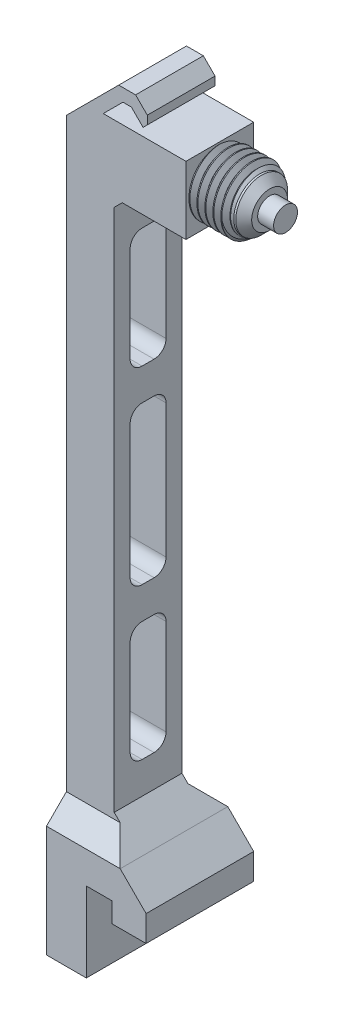
SolidWorks part; units mm, degrees
ref_plane "Front Plane" through (0, 0, 0) normal (0, 0, 1) x (1, 0, 0)
ref_plane "Top Plane" through (0, 0, 0) normal (0, 1, 0) x (1, 0, 0)
ref_plane "Right Plane" through (0, 0, 0) normal (1, 0, 0) x (0, 0, -1)
sketch "Sketch1" plane through (0, 0, 0) normal (0, 0, 1) x (1, 0, 0)
  line L0 (-13, 0) -> (13, 0) construction
  line L1 (-3, 12) -> (-3, -12) construction
  line L2 (-13, 12) -> (-13, -12) construction
  line L3 (13, 8) -> (13, -8) construction
  point P8 (6, -8)
  dimension "Thread Dia" = 16
  dimension "Hex" = 24
  dimension "Head Ht" = 10
  dimension "Length" = 16
  dimension "D1" = 7
ref_plane "Plane2" through (13, 0, 0) normal (1, 0, 0) x (0, 0, -1)
sketch "Sketch2" plane through (13, 0, 0) normal (1, 0, 0) x (0, 0, -1)
  circle A0 centre (0, 0) radius 8
extrude "Boss-Extrude1" add sketch "Sketch2" against normal up to vertex (16 mm away) up to point (-3, -12, 0)
sketch "Sketch4" plane through (13, 0, 0) normal (1, 0, 0) x (0, 0, -1)
  circle A1 centre (0, 0) radius 8
  circle A2 centre (0, 0) radius 8
  dimension "D1" = 0
curve "Helix/Spiral1" pitch 2 height 18 turns 9 parameters "Pitch"=2
chamfer "Chamfer1" distance 1.5 angle 45 1 edges at (13, 0, -8)
sketch "Sketch5" plane through (0, 0, 0) normal (0, 0, 1) x (1, 0, 0)
  line L0 (13, 8) -> (13.75, 6.701)
  line L1 (13.75, 6.701) -> (14, 6.701)
  line L2 (14, 6.701) -> (14.75, 8)
  line L3 (13, 8) -> (14.75, 8)
  line L4 (13.875, 6.701) -> (13.875, 8) construction
  line L5 (13.375, 7.3505) -> (14.375, 7.3505) construction
  line L6 (13, -8) -> (13, 8) construction
  dimension "D1" = 60
  dimension "D2" = 0.25
  dimension "D3" = 1
sweep "Cut-Sweep1" cut profiles "Sketch5" path "Helix/Spiral1" align with end faces yes
sketch "Sketch3" plane through (-3, 0, 0) normal (-1, 0, 0) x (0, 0, 1)
  line L0 (0, 12) -> (0, -12) construction
  line L1 (-12, -6.9282) -> (0, -13.8564)
  line L2 (0, -13.8564) -> (12, -6.9282)
  line L3 (12, -6.9282) -> (12, 6.9282)
  line L4 (12, 6.9282) -> (0, 13.8564)
  line L5 (0, 13.8564) -> (-12, 6.9282)
  line L6 (-12, 6.9282) -> (-12, -6.9282)
  circle A0 centre (0, 0) radius 12 construction
extrude "Boss-Extrude2" add sketch "Sketch3" along normal up to vertex (10 mm away) up to point (-13, -12, 0)
sketch "Sketch6" plane through (-13, 0, 0) normal (-1, 0, 0) x (0, 0, 1)
  circle A0 centre (0, 0) radius 12 construction
  circle A1 centre (0, 0) radius 12
extrude "Cut-Extrude1" cut sketch "Sketch6" against normal through all draft 60 flip side to cut
sketch "Sketch7" plane through (-13, 0, 0) normal (-1, 0, 0) x (0, 0, 1)
  line L0 (0, 0) -> (0, 12) construction
  line L2 (0, 12) -> (0, -12) construction
  line L3 (-10.3923, 6) -> (10.3923, 6) construction
  circle A1 centre (0, 0) radius 12 construction
  text T0 "8.8\r\n" font "Arial" height in points 16
  point P8 (0, 6)
extrude "Cut-Extrude2" cut sketch "Sketch7" against normal blind 0.25
sketch "Sketch9" plane through (0, 0, 0) normal (0, 0, 1) x (1, 0, 0)
  line L0 (-3, 8) -> (-3, 0)
  line L1 (-3, 0) -> (-5, 0)
  line L2 (-5, 0) -> (-13, 8)
  line L3 (-13, 8) -> (-3, 8)
  line L4 (-13, 0) -> (13, 0) construction
  line L5 (-3, 12) -> (-3, -12) construction
  line L6 (13, 8) -> (13, -8) construction
  dimension "D1" = 45
  dimension "MinThreadLg" = 26
revolve "Revolve1" [suppressed] add sketch "Sketch9" angle 360 about L1
sketch "Sketch10" plane through (13, 0, 0) normal (1, 0, 0) x (0, 0, -1)
  circle A0 centre (0, 0) radius 6.5
extrude "Boss-Extrude3" add sketch "Sketch10" along normal blind 2.5
chamfer "Chamfer2" distance 2 angle 45 1 edges at (15.5, 0, -6.5)
sketch "Sketch11" plane through (15.5, 0, 0) normal (1, 0, 0) x (0, 0, -1)
  circle A0 centre (0, 0) radius 3
  dimension "D1" = 6
extrude "Boss-Extrude4" add sketch "Sketch11" along normal blind 4
sketch "Sketch13" plane through (-3, 0, 0) normal (1, 0, 0) x (0, 0, -1)
  line L1 (23.7718, -25.4479) -> (-27.8908, -25.4479)
  line L2 (23.7718, -25.4479) -> (23.7718, 26.4267)
  line L3 (23.7718, 26.4267) -> (-27.8908, 26.4267)
  line L4 (-27.8908, -25.4479) -> (-27.8908, 26.4267)
extrude "Cut-Extrude3" cut sketch "Sketch13" against normal blind 16 and the other way blind 6
sketch "Sketch14" plane through (3, 0, 0) normal (-1, 0, 0) x (0, 0, 1)
  line L1 (-8.5, -8.5) -> (8.5, -8.5)
  line L2 (-8.5, -8.5) -> (-8.5, 8.5)
  line L3 (-8.5, 8.5) -> (8.5, 8.5)
  line L4 (8.5, -8.5) -> (8.5, 8.5)
  line L5 (-8.5, -8.5) -> (8.5, 8.5) construction
  line L6 (-8.5, 8.5) -> (8.5, -8.5) construction
  point P0 (0, 0)
  dimension "D1" = 17
  dimension "D2" = 17
extrude "Boss-Extrude5" add sketch "Sketch14" along normal blind 30
sketch "Sketch15" plane through (0, -8.5, 0) normal (0, -1, 0) x (1, 0, 0)
  line L0 (-27, 8.5) -> (3, 8.5) construction
  line L1 (-27, -8.5) -> (-15, -8.5)
  line L2 (-27, -8.5) -> (-27, 8.5)
  line L3 (-27, 8.5) -> (-15, 8.5)
  line L4 (-15, -8.5) -> (-15, 8.5)
  dimension "D1" = 12
extrude "Boss-Extrude6" add sketch "Sketch15" along normal blind 140
chamfer "Chamfer3" distance 5 angle 45 1 edges at (-27, 8.5, 0)
sketch "Sketch17" plane through (0, 0, 8.5) normal (0, 0, 1) x (1, 0, 0)
  line L0 (-15, -148.5) -> (-15, -8.5) construction
  line L1 (-27, -148.5) -> (-7, -148.5)
  line L2 (-27, -148.5) -> (-27, -186.5)
  line L3 (-27, -186.5) -> (-17, -186.5)
  line L4 (-17, -156.5) -> (-17, -186.5)
  line L5 (-10.5, -161.5) -> (-2, -161.5)
  line L7 (-7, -148.5) -> (-2, -148.5)
  line L8 (-2, -161.5) -> (-2, -148.5)
  line L11 (-17, -156.5) -> (-10.5, -156.5)
  line L12 (-10.5, -161.5) -> (-10.5, -156.5)
  line M10 (-27, -148.5) -> (-15, -148.5)
  dimension "D1" = 6.5
  dimension "D2" = 5
  dimension "D3" = 13
  dimension "D4" = 10
  dimension "D5" = 25
  dimension "D6" = 13
extrude "Boss-Extrude7" add sketch "Sketch17" against normal blind 22 and the other way blind 5 contours L12 L5 L8 L7 L2 L3 L4 L11 M10
sketch "Sketch18" plane through (-27, 0, 0) normal (-1, 0, 0) x (0, 0, 1)
  line L1 (-13.5, -156.5) -> (13.5, -156.5) construction
  circle A0 centre (0, -164.5) radius 1.75
  dimension "D1" = 3.5
  dimension "D2" = 8
extrude "Cut-Extrude5" cut sketch "Sketch18" against normal blind 17
chamfer "Chamfer5" distance 2 angle 45 1 edges at (-15, -8.5, 0)
sketch "Sketch20" plane through (0, 0, 8.5) normal (0, 0, 1) x (1, 0, 0)
  line L0 (-22, 8.5) -> (-11.7574, 18.7426)
  line L1 (-11.7574, 14.5) -> (-7.7574, 10.5)
  line L2 (-7.7574, 10.5) -> (-5.636, 12.6213)
  line L3 (-5.636, 12.6213) -> (-11.7574, 18.7426)
  line L6 (-11.7574, 14.5) -> (-17.7574, 8.5)
  line L7 (-22, 8.5) -> (3, 8.5) construction
  line L8 (-17.7574, 8.5) -> (-22, 8.5)
  dimension "D1" = 3
  dimension "D2" = 3
  dimension "D3" = 2
  dimension "D4" = 6
extrude "Boss-Extrude8" add sketch "Sketch20" against normal blind 17
chamfer "Chamfer7" distance 1.5 angle 45 1 edges at (-11.7574, 14.5, 0)
chamfer "Chamfer8" distance 1.5 angle 45 1 edges at (-5.636, 12.6213, 0)
chamfer "Chamfer10" distance 3 angle 45 1 edges at (-11.7574, 18.7426, 0)
chamfer "Chamfer11" distance 6.5 angle 45 2 edges at (-2, -148.5, 0) (-15, -148.5, 0)
sketch "Sketch23" plane through (-15, 0, 0) normal (1, 0, 0) x (0, 0, -1)
  line L0 (-8.5, -142) -> (-8.5, -10.5) construction
  line L1 (-4.5, -18.5) -> (4.5, -18.5)
  line L2 (-4.5, -18.5) -> (-4.5, -48.5)
  line L3 (-4.5, -48.5) -> (4.5, -48.5)
  line L4 (4.5, -18.5) -> (4.5, -48.5)
  line L5 (-4.5, -18.5) -> (4.5, -48.5) construction
  line L6 (-4.5, -48.5) -> (4.5, -18.5) construction
  line L7 (8.5, -142) -> (8.5, -10.5) construction
  line L8 (8.5, -10.5) -> (-8.5, -10.5) construction
  line L9 (-4.5, -56.5) -> (4.5, -56.5)
  line L10 (-4.5, -56.5) -> (-4.5, -96)
  line L11 (-4.5, -96) -> (4.5, -96)
  line L12 (4.5, -56.5) -> (4.5, -96)
  line L13 (-4.5, -104) -> (4.5, -104)
  line L14 (-4.5, -104) -> (-4.5, -134)
  line L15 (-4.5, -134) -> (4.5, -134)
  line L16 (4.5, -104) -> (4.5, -134)
  line L17 (-8.5, -142) -> (8.5, -142) construction
  point P0 (0, -33.5)
  dimension "D1" = 30
  dimension "D2" = 4
  dimension "D3" = 4
  dimension "D4" = 8
  dimension "D5" = 8
  dimension "D6" = 8
  dimension "D7" = 8
  dimension "D8" = 30
extrude "Cut-Extrude7" cut sketch "Sketch23" against normal blind 20
fillet "Fillet1" radius 3 12 edges at (-21, -134, -4.5) (-21, -134, 4.5) (-21, -104, -4.5) (-21, -104, 4.5) (-21, -56.5, 4.5) (-21, -56.5, -4.5) (-21, -96, -4.5) (-21, -96, 4.5) (-21, -48.5, 4.5) (-21, -48.5, -4.5) (-21, -18.5, 4.5) (-21, -18.5, -4.5)
chamfer "Chamfer12" distance 5 angle 45 2 edges at (-17.75, -148.5, 8.5) (-17.75, -148.5, -8.5)
sketch "Sketch25" plane through (-27, 0, 0) normal (-1, 0, 0) x (0, 0, 1)
  line L0 (13.5, -186.5) -> (-13.5, -186.5) construction
  line L1 (-13.5, -176.5) -> (13.5, -176.5)
  line L2 (-13.5, -176.5) -> (-13.5, -186.5)
  line L3 (-13.5, -186.5) -> (13.5, -186.5)
  line L4 (13.5, -176.5) -> (13.5, -186.5)
  line L5 (-13.5, -148.5) -> (-13.5, -186.5) construction
  line L6 (13.5, -148.5) -> (13.5, -186.5) construction
  circle A0 centre (0, -164.5) radius 1.75 construction
  dimension "D1" = 0
  dimension "D2" = 0
  dimension "D3" = 0
  dimension "D4" = 12
extrude "Cut-Extrude8" cut sketch "Sketch25" against normal blind 10
equation "\"D2@Sketch5\" = \"Pitch@Helix/Spiral1\"*.125"
equation "\"D3@Sketch5\" = \"Pitch@Helix/Spiral1\"*.50"
equation "\"D3@Helix/Spiral1\" = \"Length@Sketch1\"+\"Pitch@Helix/Spiral1\""
equation "\"D1@Chamfer1\" = \"Pitch@Helix/Spiral1\"*.750"
equation "\"D1@Sketch1\" = \"Pitch@Helix/Spiral1\"*3.50"
